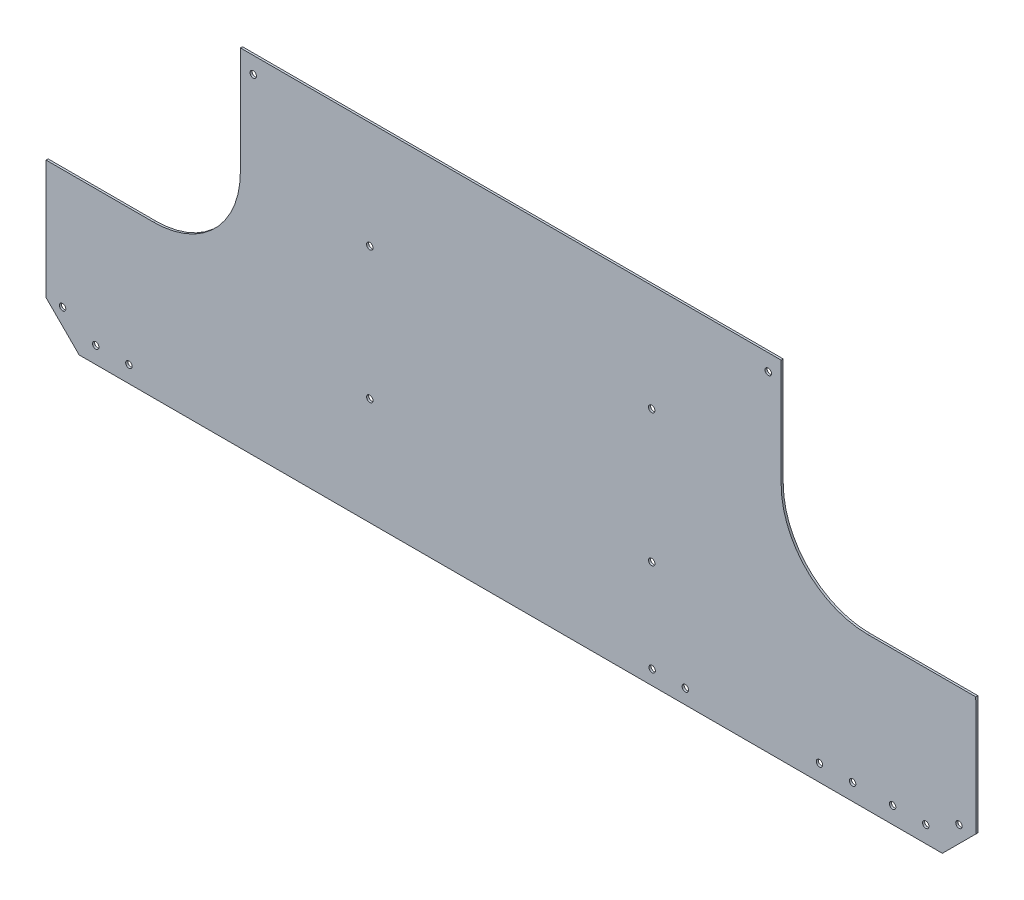
SolidWorks part; units mm, degrees
material "Perspex (TM) GS Acrylic Cast Sheet"
ref_plane "Front Plane" through (0, 0, 0) normal (0, 0, 1) x (1, 0, 0)
ref_plane "Top Plane" through (0, 0, 0) normal (0, 1, 0) x (1, 0, 0)
ref_plane "Right Plane" through (0, 0, 0) normal (1, 0, 0) x (0, 0, -1)
sketch "Sketch1" plane through (0, 0, 0) normal (0, 0, 1) x (1, 0, 0)
  line L1 (-457.2, -304.8) -> (457.2, -304.8)
  line L2 (-457.2, -304.8) -> (-457.2, 304.8)
  line L3 (-457.2, 304.8) -> (457.2, 304.8)
  line L4 (457.2, -304.8) -> (457.2, 304.8)
  line L5 (0, 304.8) -> (0, -304.8) construction
  line L6 (-457.2, 0) -> (457.2, 0) construction
  point P0 (0, 0)
  point P4 (-320.04, 0)
  point P5 (320.04, 0)
  point P6 (0, 213.36)
  point P7 (0, -213.36)
  dimension "Length" = 914.4
  dimension "Width" = 609.6
  dimension "Break" = 137.16
  dimension "D2" = 137.16
  dimension "D1" = 91.44
  dimension "D3" = 91.44
sketch "Sketch2" plane through (0, 0, 0) normal (1, 0, 0) x (0, 0, -1)
  line L0 (-0.7938, -304.8) -> (0.7938, -304.8)
  dimension "Thickness" = 1.5875
sketch "Sketch3" plane through (0, 0, 0) normal (0, 0, 1) x (1, 0, 0)
  line L0 (-457.2, -304.8) -> (-457.2, 304.8) construction
  line L1 (-457.2, -304.8) -> (457.2, -304.8) construction
  line L2 (457.2, -304.8) -> (457.2, 304.8) construction
  line L3 (-457.2, 304.8) -> (457.2, 304.8) construction
  line L4 (-457.2, -304.8) -> (-457.2, 304.8)
  line L5 (-457.2, -304.8) -> (457.2, -304.8)
  line L6 (457.2, -304.8) -> (457.2, 304.8)
  line L7 (-457.2, 304.8) -> (457.2, 304.8)
extrude "Boss-Extrude1" add sketch "Sketch3" along normal mid plane 1.5875
sketch "Sketch4" plane through (0, 0, 0.7937) normal (0, 0, 1) x (1, 0, 0)
  line L0 (-378.2467, -279.4) -> (-378.2467, -39.3705)
  line L1 (-457.2, -304.8) -> (457.2, -304.8) construction
  line L2 (-378.2467, -751.2581) -> (-378.2467, -65.4581) construction
  line L3 (-378.2467, -39.3705) -> (333.614, -39.3705)
  line L4 (333.614, -39.3705) -> (333.9807, -279.0843)
  line L5 (333.6645, -317.5147) -> (333.6645, -266.7147) construction
  line L6 (333.6645, -304.8) -> (457.2, -304.8)
  line L7 (457.2, -304.8) -> (457.2, 304.8)
  line L8 (457.2, 304.8) -> (-457.2, 304.8)
  line L9 (-457.2, 304.8) -> (-457.2, -304.8)
  line L10 (-457.2, -304.8) -> (-378.2467, -304.8)
  line L11 (-378.2467, -304.8) -> (-352.8467, -304.8)
  line L12 (-352.8467, -751.2581) -> (-352.8467, -65.4581) construction
  line L13 (-352.8467, -304.8) -> (-378.2467, -279.4)
  line L14 (333.6645, -304.8) -> (308.2651, -304.8)
  line L15 (308.2651, -39.3463) -> (308.2651, -725.1463) construction
  line L16 (308.2651, -304.8) -> (333.9807, -279.0843)
extrude "Cut-Extrude1" cut sketch "Sketch4" against normal blind 2.54
sketch "Sketch7" plane through (0, 0, 0.7937) normal (0, 0, 1) x (1, 0, 0)
  line L0 (-378.2467, -188.1903) -> (-378.2467, -39.3463)
  line L3 (-378.2467, -39.3463) -> (-229.4027, -39.3463)
  line L10 (-229.4027, -64.7463) -> (-229.4027, -39.3463)
  line L11 (-229.4027, -64.7463) -> (-229.4027, -121.8963)
  line L12 (-352.8467, -188.1903) -> (-295.6967, -188.1903)
  line L13 (-352.8467, -188.1903) -> (-378.2467, -188.1903)
  arc A1 (-229.4027, -121.8963) -> (-295.6967, -188.1903) centre (-295.6967, -121.8963) cw
extrude "Cut-Extrude2" cut sketch "Sketch7" against normal blind 2.54
sketch "Sketch8" plane through (0, 0, 0.7937) normal (0, 0, 1) x (1, 0, 0)
  line L6 (251.1151, -188.1903) -> (336.8401, -188.1903)
  line L7 (336.8401, -188.1903) -> (336.8401, -36.1713)
  line L8 (184.8211, -36.1713) -> (336.8401, -36.1713)
  line L9 (184.8211, -121.8963) -> (184.8211, -36.1713)
  arc A1 (184.8211, -121.8963) -> (251.1151, -188.1903) centre (251.1151, -121.8963) ccw
extrude "Cut-Extrude3" cut sketch "Sketch8" against normal blind 2.54
sketch "Sketch9" plane through (0, 0, 0.7937) normal (0, 0, 1) x (1, 0, 0)
  point P0 (-365.5467, -279.4147)
  point P1 (-340.1467, -292.1147)
  point P3 (-314.7467, -292.1147)
  point P5 (-365.5467, -229.8463)
  point P7 (86.0055, -293.7022)
  point P9 (111.4055, -293.7022)
  point P11 (214.1495, -292.1147)
  point P13 (239.5495, -292.1147)
  point P15 (270.1645, -292.1147)
  point P17 (295.5645, -292.1147)
  point P19 (320.9645, -279.4147)
  point P21 (320.9651, -229.8463)
  point P23 (-219.4967, -52.0463)
  point P25 (174.9151, -52.0463)
hole_wizard "#10 (0.1935) Diameter Hole1" positions "Sketch10" profile "Sketch11" hole size "#10" standard "ANSI Inch" end condition through all
sketch "Sketch10" plane through (0, 0, 0.7937) normal (0, 0, 1) x (1, 0, 0)
  point P0 (-314.7467, -292.1147)
  point P3 (-340.1467, -292.1147)
  point P6 (-365.5467, -279.4147)
  point P9 (86.0055, -293.7022)
  point P12 (111.4055, -293.7022)
  point P15 (214.1495, -292.1147)
  point P18 (239.5495, -292.1147)
  point P21 (295.5645, -292.1147)
  point P24 (270.1645, -292.1147)
  point P27 (320.9645, -279.4147)
  point P31 (174.9151, -52.0463)
  point P34 (-219.4967, -52.0463)
sketch "Sketch11" plane through (-314.7467, -292.1147, 0.7937) normal (1, 0, 0) x (0, -1, 0)
  line L0 (0, 0) -> (0, 1.5875)
  line L1 (0, 1.5875) -> (2.4574, 1.5875)
  line L2 (2.4574, 1.5875) -> (2.4574, 0)
  line L5 (2.4574, 0) -> (0, 0)
  line L11 (0, -6.35) -> (0, 107.95) construction
  dimension "Thru Hole Dia." = 4.9149
  dimension "Thru Hole Depth" = 1.5875
sketch "Sketch12" plane through (0, 0, 0.7937) normal (0, 0, 1) x (1, 0, 0)
  line L0 (-22.2908, -304.8) -> (-22.2908, -39.3463)
  line L1 (-352.8467, -304.8) -> (308.2651, -304.8) construction
  line L3 (-378.2467, -39.3463) -> (307.5533, -39.3463) construction
  line L8 (-130.2408, -222.8732) -> (85.6592, -222.8732)
  line L10 (-130.2408, -222.8732) -> (-130.2408, -121.2732)
  line L11 (-130.2408, -121.2732) -> (85.6592, -121.2732)
  line L12 (85.6592, -222.8732) -> (85.6592, -121.2732)
  line L13 (-130.2408, -222.8732) -> (85.6592, -121.2732) construction
  line L14 (-130.2408, -121.2732) -> (85.6592, -222.8732) construction
  point P6 (-22.2908, -172.0732)
  point P16 (-22.2908, -304.8)
hole_wizard "#10 (0.1935) Diameter Hole2" positions "Sketch13" profile "Sketch14" hole size "#10" standard "ANSI Inch" end condition through all
sketch "Sketch13" plane through (0, 0, 0.7937) normal (0, 0, 1) x (1, 0, 0)
  line L0 (-130.2408, -222.8732) -> (-130.2408, -121.2732) construction
  point P25 (-130.2408, -121.2732)
  point P28 (-130.2408, -222.541)
  point P32 (85.6592, -222.8732)
  point P35 (85.6592, -121.2732)
sketch "Sketch14" plane through (-130.2408, -121.2732, 0.7937) normal (1, 0, 0) x (0, -1, 0)
  line L0 (0, 0) -> (0, 1.5875)
  line L1 (0, 1.5875) -> (2.4574, 1.5875)
  line L2 (2.4574, 1.5875) -> (2.4574, 0)
  line L5 (2.4574, 0) -> (0, 0)
  line L11 (0, -6.35) -> (0, 107.95) construction
  dimension "Thru Hole Dia." = 4.9149
  dimension "Thru Hole Depth" = 1.5875
equation "\"D1@Boss-Extrude1\"=\"thickness@sketch2\""
equation "\"Break@Sketch1\" = \"Length@Sketch1\" * 0.15"
equation "\"D2@Sketch1\" = \"Break@Sketch1\""
equation "\"D1@Sketch1\"=\"Width@Sketch1\"*0.15"
equation "\"D3@Sketch1\"=\"D1@Sketch1\""
